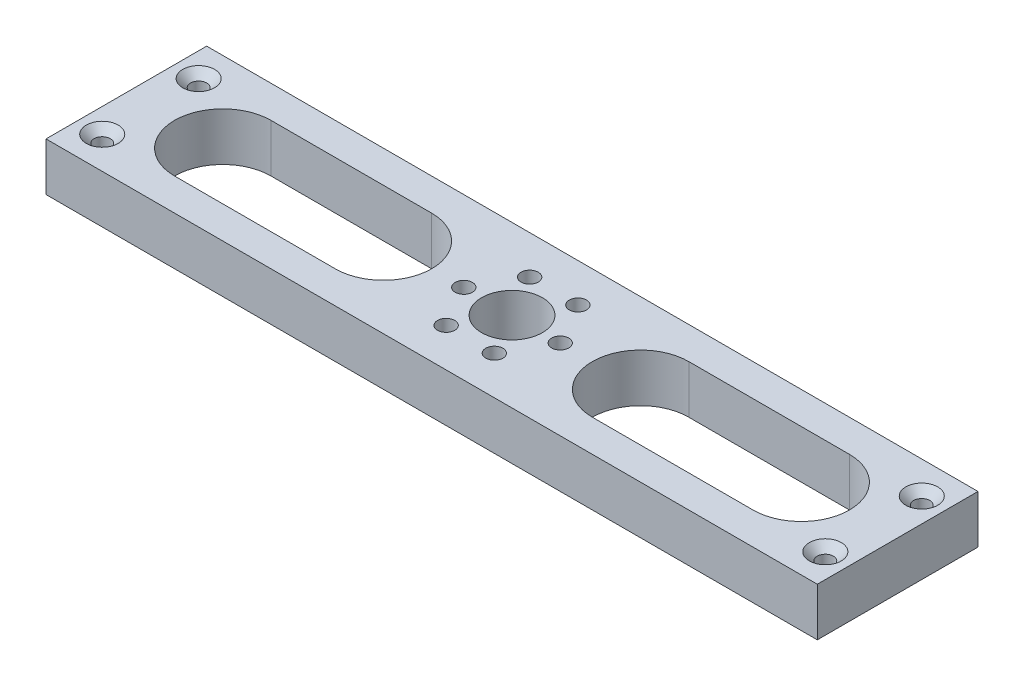
SolidWorks part; units mm, degrees
material "6061 Alloy"
ref_plane "Front Plane" through (0, 0, 0) normal (0, 0, 1) x (1, 0, 0)
ref_plane "Top Plane" through (0, 0, 0) normal (0, 1, 0) x (1, 0, 0)
ref_plane "Right Plane" through (0, 0, 0) normal (1, 0, 0) x (0, 0, -1)
sketch "Sketch1" plane through (0, 0, 0) normal (0, 1, 0) x (1, 0, 0)
  line L1 (-76.2, -15.875) -> (76.2, -15.875)
  line L2 (-76.2, -15.875) -> (-76.2, 15.875)
  line L3 (-76.2, 15.875) -> (76.2, 15.875)
  line L4 (76.2, -15.875) -> (76.2, 15.875)
  line L5 (-76.2, -15.875) -> (76.2, 15.875) construction
  line L6 (-76.2, 15.875) -> (76.2, -15.875) construction
  point P0 (0, 0)
  dimension "D1" = 152.4
  dimension "D2" = 31.75
extrude "Boss-Extrude1" add sketch "Sketch1" along normal mid plane 9.525
sketch "Sketch3" plane through (0, 4.7625, 0) normal (0, 1, 0) x (1, 0, 0)
  point P6 (71.4375, -9.525)
  point P9 (71.4375, 9.525)
  point P10 (-71.4375, -9.525)
  point P13 (-71.4375, 9.525)
hole_wizard "CSK for M3 Flat Head Machine Screw1" positions "Sketch4" profile "Sketch6" countersink size "M3" standard "ANSI Metric" end condition through all
sketch "Sketch4" plane through (0, 4.7625, 0) normal (0, 1, 0) x (1, 0, 0)
  point P18 (-71.4375, -9.525)
  point P24 (71.4375, -9.525)
  point P27 (71.4375, 9.525)
  point P32 (-71.4375, 9.525)
sketch "Sketch6" plane through (-71.4375, 4.7625, 9.525) normal (1, 0, 0) x (0, 0, 1)
  line L0 (0, 0) -> (0, 9.525)
  line L1 (0, 9.525) -> (1.6, 9.525)
  line L2 (1.6, 9.525) -> (1.6, 1.55)
  line L3 (1.6, 1.55) -> (3.15, 0)
  line L5 (3.15, 0) -> (0, 0)
  line L6 (-1.6, 1.55) -> (-3.15, 0) construction
  line L11 (0, -6.35) -> (0, 107.95) construction
  dimension "Thru Hole Dia." = 3.2
  dimension "Thru Hole Depth" = 9.525
  dimension "Near C'Sink Dia." = 6.3
  dimension "Near C'Sink Angle" = 90
sketch "Sketch7" plane through (0, -4.7625, 0) normal (0, -1, 0) x (1, 0, 0)
  point P0 (0, 0)
hole_wizard "Ø12.0mm Dowel Hole1" positions "Sketch8" profile "Sketch9" hole size "Ø12.0" standard "ANSI Metric" end condition through all
sketch "Sketch8" plane through (0, -4.7625, 0) normal (0, -1, 0) x (-1, 0, 0)
  point P0 (0, 0)
sketch "Sketch9" plane through (0, -4.7625, 0) normal (1, 0, 0) x (0, 0, -1)
  line L0 (0, 0) -> (0, 9.525)
  line L1 (0, 9.525) -> (6, 9.525)
  line L2 (6, 9.525) -> (6, 0)
  line L5 (6, 0) -> (0, 0)
  line L11 (0, -6.35) -> (0, 107.95) construction
  dimension "Thru Hole Dia." = 12
  dimension "Thru Hole Depth" = 9.525
sketch "Sketch11" plane through (0, -4.7625, 0) normal (0, -1, 0) x (1, 0, 0)
  point P9 (-4.7625, 8.2489)
  point P11 (4.7625, 8.2489)
  point P13 (9.525, 0)
  point P15 (-9.525, 0)
  point P17 (-4.7625, -8.2489)
  point P19 (4.7625, -8.2489)
hole_wizard "CBORE for M3 SHCS1" positions "Sketch12" profile "Sketch14" counterbore size "M3" standard "ANSI Metric" end condition through all
sketch "Sketch12" plane through (0, -4.7625, 0) normal (0, -1, 0) x (-1, 0, 0)
  point P19 (4.7625, -8.2489)
  point P22 (9.525, 0)
  point P25 (4.7625, 8.2489)
  point P28 (-4.7625, 8.2489)
  point P31 (-9.525, 0)
  point P34 (-4.7625, -8.2489)
sketch "Sketch14" plane through (-4.7625, -4.7625, 8.2489) normal (1, 0, 0) x (0, 0, -1)
  line L0 (0, 0) -> (0, 9.525)
  line L1 (0, 9.525) -> (1.7, 9.525)
  line L3 (1.7, 9.525) -> (1.7, 2)
  line L4 (1.7, 2) -> (2.25, 2)
  line L5 (2.25, 2) -> (2.25, 0)
  line L7 (2.25, 0) -> (0, 0)
  line L11 (0, -6.35) -> (0, 107.95) construction
  dimension "Thru Hole Dia." = 3.4
  dimension "Thru Hole Depth" = 9.525
  dimension "C'Bore Dia." = 4.5
  dimension "C'Bore Depth" = 2
sketch "Sketch15" plane through (0, 4.7625, 0) normal (0, 1, 0) x (1, 0, 0)
  line L0 (-57.15, 0) -> (-25.4, 0) construction
  line L1 (-5.2388, 0) -> (5.2388, 0) construction
  line L2 (-57.15, 9.525) -> (-25.4, 9.525)
  line L3 (-57.15, -9.525) -> (-25.4, -9.525)
  line L4 (25.4, 0) -> (57.15, 0) construction
  line L5 (25.4, 9.525) -> (57.15, 9.525)
  line L6 (25.4, -9.525) -> (57.15, -9.525)
  line L7 (-25.4, 0) -> (25.4, 0) construction
  line L8 (0, -5.2388) -> (0, 5.2388) construction
  arc A0 (-57.15, 9.525) -> (-57.15, -9.525) centre (-57.15, 0) ccw
  arc A1 (-25.4, -9.525) -> (-25.4, 9.525) centre (-25.4, 0) ccw
  arc A2 (25.4, 9.525) -> (25.4, -9.525) centre (25.4, 0) ccw
  arc A3 (57.15, -9.525) -> (57.15, 9.525) centre (57.15, 0) ccw
  point P5 (-41.275, 0)
  point P10 (41.275, 0)
  point P19 (0, 0)
  dimension "D1" = 19.05
  dimension "D2" = 25.4
  dimension "D3" = 31.75
extrude "Cut-Extrude1" cut sketch "Sketch15" against normal through all
